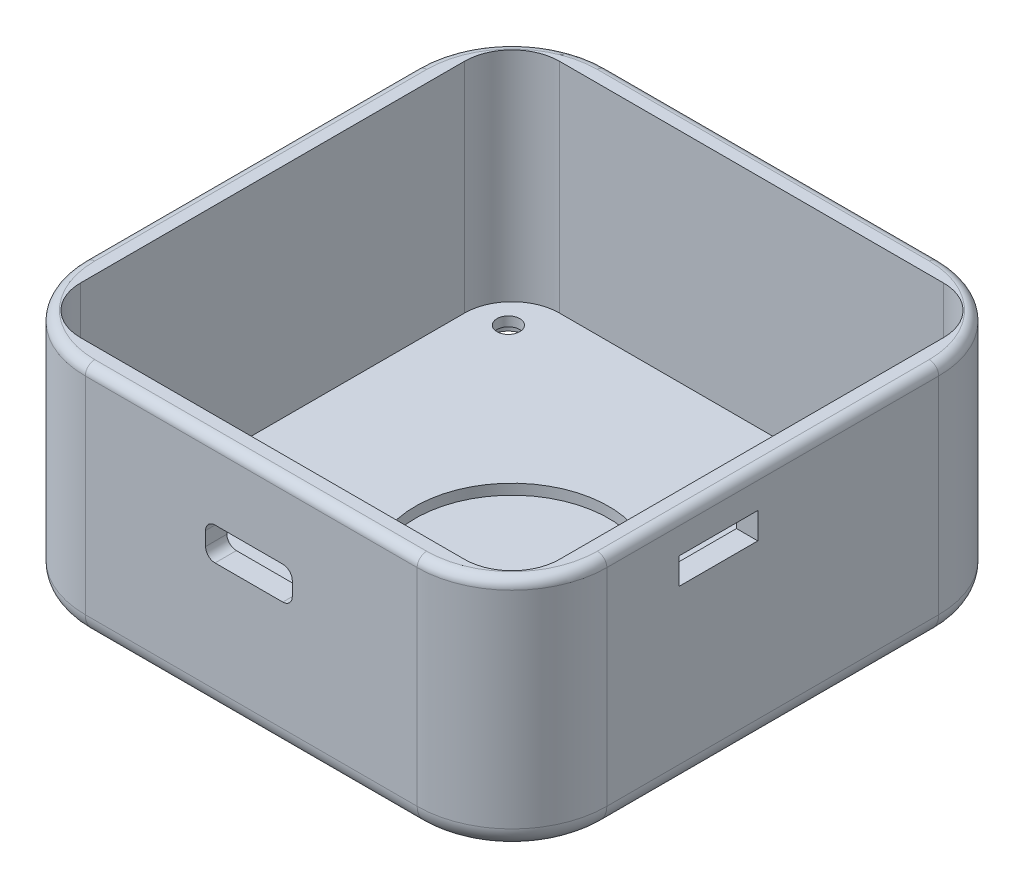
SolidWorks part; units mm, degrees
ref_plane "前视基准面" through (0, 0, 0) normal (0, 0, 1) x (1, 0, 0)
ref_plane "上视基准面" through (0, 0, 0) normal (0, 1, 0) x (1, 0, 0)
ref_plane "右视基准面" through (0, 0, 0) normal (1, 0, 0) x (0, 0, -1)
other "Configuration Table"
sketch "草图1" plane through (0, 0, 0) normal (0, 1, 0) x (1, 0, 0)
  line L1 (-17.5, 27.5) -> (17.5, 27.5)
  line L2 (-27.5, 17.5) -> (-27.5, -17.5)
  line L3 (-17.5, -27.5) -> (17.5, -27.5)
  line L4 (27.5, 17.5) -> (27.5, -17.5)
  line L5 (-27.5, 27.5) -> (27.5, -27.5) construction
  line L6 (-27.5, -27.5) -> (27.5, 27.5) construction
  arc A0 (-17.5, -27.5) -> (-27.5, -17.5) centre (-17.5, -17.5) cw
  arc A1 (17.5, -27.5) -> (27.5, -17.5) centre (17.5, -17.5) ccw
  arc A2 (27.5, 17.5) -> (17.5, 27.5) centre (17.5, 17.5) ccw
  arc A3 (-17.5, 27.5) -> (-27.5, 17.5) centre (-17.5, 17.5) ccw
  point P0 (0, 0)
  point P6 (0, 0)
  point P26 (25.25, -25.25)
  point P29 (25.25, 25.25)
  point P33 (-25.25, 25.25)
  dimension "D5" = 10
  dimension "D1" = 55
  dimension "D2" = 55
  dimension "D3" = 50.5
  dimension "D4" = 50.5
extrude "凸台-拉伸2" add sketch "草图1" along normal blind 25 contours L2 A0 L3 A1 L4 A2 L1 A3
sketch "草图3" plane through (0, 25, 0) normal (0, 1, 0) x (1, 0, 0)
  line L1 (-20.25, 25.25) -> (20.25, 25.25)
  line L2 (-25.25, 20.25) -> (-25.25, -20.25)
  line L3 (-20.25, -25.25) -> (20.25, -25.25)
  line L4 (25.25, 20.25) -> (25.25, -20.25)
  line L5 (0, -25.25) -> (0, 25.25) construction
  line L6 (-25.25, 0) -> (25.25, 0) construction
  arc A0 (-20.25, -25.25) -> (-25.25, -20.25) centre (-20.25, -20.25) cw
  arc A1 (20.25, -25.25) -> (25.25, -20.25) centre (20.25, -20.25) ccw
  arc A2 (25.25, 20.25) -> (20.25, 25.25) centre (20.25, 20.25) ccw
  arc A3 (-20.25, 25.25) -> (-25.25, 20.25) centre (-20.25, 20.25) ccw
  point P0 (0, 0)
  point P8 (25.25, -25.25)
  point P11 (25.25, 25.25)
  point P15 (-25.25, 25.25)
  dimension "D3" = 5
  dimension "D1" = 50.5
  dimension "D2" = 50.5
extrude "切除-拉伸1" cut sketch "草图3" against normal blind 23 contours L2 A0 L3 A1 L4 A2 L1 A3
sketch "草图4" plane through (0, 0, 0) normal (0, -1, 0) x (1, 0, 0)
  circle A0 centre (-21.4527, 21.3084) radius 1.2
  circle A1 centre (21.3084, 20.9274) radius 1.2
  circle A2 centre (-21.8337, -21.4527) radius 1.2
  circle A3 centre (20.9274, -21.8337) radius 1.2
extrude "切除-拉伸2" cut sketch "草图4" against normal blind 10
sketch "草图5" plane through (0, 0, 0) normal (0, -1, 0) x (1, 0, 0)
  circle A0 centre (-21.4527, 21.3084) radius 2.05
  circle A1 centre (21.3084, 20.9274) radius 2.05
  circle A2 centre (-21.8337, -21.4527) radius 2.05
  circle A3 centre (20.9274, -21.8337) radius 2.05
extrude "切除-拉伸3" cut sketch "草图5" against normal blind 1
sketch "草图7" plane through (0, 0, 27.5) normal (0, 0, 1) x (1, 0, 0)
  line L0 (-3.2936, 15.5) -> (2.8063, 15.5) construction
  line L2 (-3.8156, 17.2307) -> (3.3283, 17.2307)
  line L3 (-4.8156, 16.2307) -> (-4.8156, 14.7693)
  line L4 (-3.8156, 13.7693) -> (3.3283, 13.7693)
  line L5 (4.3283, 16.2307) -> (4.3283, 14.7693)
  line L6 (-0.2436, 13.7693) -> (-0.2436, 17.2307) construction
  line L7 (-4.8156, 15.5) -> (4.3283, 15.5) construction
  arc A0 (-3.2436, 15.55) -> (-3.2436, 15.45) centre (-3.2436, 15.5) ccw construction
  arc A1 (2.7563, 15.45) -> (2.7563, 15.55) centre (2.7563, 15.5) ccw construction
  arc A2 (3.3283, 13.7693) -> (4.3283, 14.7693) centre (3.3283, 14.7693) ccw
  arc A3 (-3.8156, 13.7693) -> (-4.8156, 14.7693) centre (-3.8156, 14.7693) cw
  arc A4 (4.3283, 16.2307) -> (3.3283, 17.2307) centre (3.3283, 16.2307) ccw
  arc A5 (-4.8156, 16.2307) -> (-3.8156, 17.2307) centre (-3.8156, 16.2307) cw
  point P8 (-0.2436, 15.5)
  dimension "D1" = 1
extrude "切除-拉伸4" cut sketch "草图7" against normal blind 8
sketch "草图8" plane through (27.5, 0, 0) normal (1, 0, 0) x (0, 0, -1)
  line L5 (-5.7254, 18.5694) -> (-5.7254, 21.1694) construction
  line L7 (-9.8734, 21.259) -> (-1.5773, 21.259)
  line L8 (-9.8734, 21.259) -> (-9.8734, 18.4797)
  line L9 (-9.8734, 18.4797) -> (-1.5773, 18.4797)
  line L10 (-1.5773, 21.259) -> (-1.5773, 18.4797)
  line L11 (-5.7254, 18.4797) -> (-5.7254, 21.259) construction
  line L12 (-9.8734, 19.8694) -> (-1.5773, 19.8694) construction
  point P4 (-5.7254, 19.8694)
  point P384 (-5.7254, 19.8194)
extrude "切除-拉伸9" cut sketch "草图8" against normal blind 8
sketch "草图11" plane through (0, 2, 0) normal (0, 1, 0) x (1, 0, 0)
  circle A0 centre (0, 0) radius 10.2
extrude "切除-拉伸11" cut sketch "草图11" against normal blind 1.1
fillet "圆角3" radius 2.2 8 edges at (-24.5711, 0, -24.5711) (-27.5, 0, 0) (-24.5711, 0, 24.5711) (0, 0, 27.5) (24.5711, 0, 24.5711) (0, 0, -27.5) (24.5711, 0, -24.5711) (27.5, 0, 0)
fillet "圆角4" radius 1 8 edges at (0, 25, -27.5) (24.5711, 25, -24.5711) (-24.5711, 25, -24.5711) (27.5, 25, 0) (24.5711, 25, 24.5711) (0, 25, 27.5) (-24.5711, 25, 24.5711) (-27.5, 25, 0)
